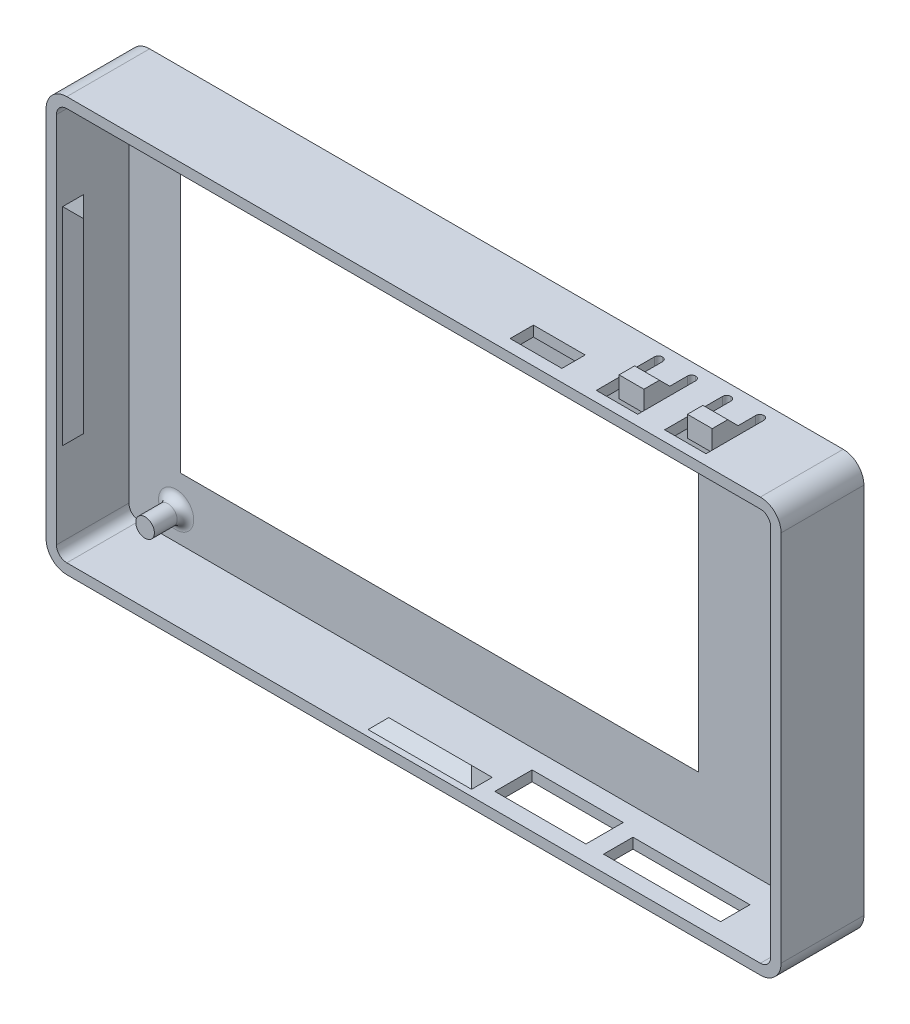
SolidWorks part; units mm, degrees
ref_plane "Front Plane" through (0, 0, 0) normal (0, 0, 1) x (1, 0, 0)
ref_plane "Top Plane" through (0, 0, 0) normal (0, 1, 0) x (1, 0, 0)
ref_plane "Right Plane" through (0, 0, 0) normal (1, 0, 0) x (0, 0, -1)
other "Graphic1"
other "Graphic (Closed) -1"
sketch "Sketch1" plane through (0, 0, 0) normal (0, 0, 1) x (1, 0, 0)
  line L1 (-33.5, 20) -> (33.5, 20)
  line L2 (-35.5, 18) -> (-35.5, -18)
  line L3 (-33.5, -20) -> (33.5, -20)
  line L4 (35.5, 18) -> (35.5, -18)
  line L5 (-35.5, 20) -> (35.5, -20) construction
  line L6 (-35.5, -20) -> (35.5, 20) construction
  arc A0 (35.5, 18) -> (33.5, 20) centre (33.5, 18) ccw
  arc A1 (35.5, -18) -> (33.5, -20) centre (33.5, -18) cw
  arc A2 (-33.5, -20) -> (-35.5, -18) centre (-33.5, -18) cw
  arc A3 (-35.5, 18) -> (-33.5, 20) centre (-33.5, 18) cw
  point P0 (0, 0)
  dimension "D3" = 2
  dimension "D1" = 71
  dimension "D2" = 40
extrude "Boss-Extrude1" add sketch "Sketch1" along normal blind 8
shell "Shell1" thickness 1
sketch "Sketch2" plane through (0, 0, 1) normal (0, 0, 1) x (1, 0, 0)
  line L0 (-35.5, 18) -> (-35.5, -18) construction
  line L1 (-29.5, 13) -> (20.5, 13)
  line L2 (-29.5, 13) -> (-29.5, -13)
  line L3 (-29.5, -13) -> (20.5, -13)
  line L4 (20.5, 13) -> (20.5, -13)
  line L5 (-29.5, 13) -> (20.5, -13) construction
  line L6 (-29.5, -13) -> (20.5, 13) construction
  point P0 (-4.5, 0)
  point P7 (-35.5, 0)
  dimension "D1" = 31
  dimension "D2" = 50
  dimension "D3" = 26
extrude "Cut-Extrude1" cut sketch "Sketch2" against normal through all
sketch "Sketch3" plane through (0, 19, 0) normal (0, -1, 0) x (1, 0, 0)
  line L0 (-33.5, 0) -> (33.5, 0) construction
  line L1 (8.15, 6.825) -> (13.15, 6.825)
  line L2 (8.15, 6.825) -> (8.15, 4.575)
  line L3 (8.15, 4.575) -> (13.15, 4.575)
  line L4 (13.15, 6.825) -> (13.15, 4.575)
  line L5 (8.15, 6.825) -> (13.15, 4.575) construction
  line L6 (8.15, 4.575) -> (13.15, 6.825) construction
  line L7 (33.5, 8) -> (33.5, 0) construction
  point P0 (10.65, 5.7)
  dimension "D1" = 5.7
  dimension "D2" = 22.85
  dimension "D3" = 5
  dimension "D4" = 2.25
extrude "Cut-Extrude2" cut sketch "Sketch3" against normal through all
sketch "Sketch4" plane through (0, 20, 0) normal (0, 1, 0) x (1, 0, 0)
  line L0 (33.5, -1) -> (-33.5, -1) construction
  line L1 (16.65, -1) -> (17.45, -1)
  line L2 (16.65, -1) -> (16.65, -7)
  line L3 (16.65, -7) -> (20.65, -7)
  line L4 (20.65, -1) -> (20.65, -7)
  line L5 (19.85, -1) -> (20.65, -1)
  line L7 (17.45, -1) -> (17.45, -5.6)
  line L8 (17.45, -5.6) -> (19.85, -5.6)
  line L9 (19.85, -1) -> (19.85, -5.6)
  line L10 (35.5, -8) -> (35.5, 0) construction
  line L11 (23.25, -1) -> (24.05, -1)
  line L12 (24.05, -1) -> (24.05, -5.6)
  line L13 (24.05, -5.6) -> (26.45, -5.6)
  line L14 (26.45, -1) -> (26.45, -5.6)
  line L15 (26.45, -1) -> (27.25, -1)
  line L16 (27.25, -1) -> (27.25, -7)
  line L17 (23.25, -7) -> (27.25, -7)
  line L18 (23.25, -1) -> (23.25, -7)
  dimension "D1" = 6
  dimension "D2" = 0.8
  dimension "D3" = 0.8
  dimension "D4" = 4
  dimension "D5" = 14.85
  dimension "D6" = 1.4
  dimension "D7" = 2
extrude "Cut-Extrude3" cut sketch "Sketch4" against normal up to surface (1 mm away) up to face at (10.65, 19, 5.7)
sketch "Sketch5" plane through (0, -20, 0) normal (0, -1, 0) x (1, 0, 0)
  line L0 (-33.5, 8) -> (33.5, 8) construction
  line L1 (6.3, 6.45) -> (15.1, 6.45)
  line L2 (6.3, 6.45) -> (6.3, 2.85)
  line L3 (6.3, 2.85) -> (15.1, 2.85)
  line L4 (15.1, 6.45) -> (15.1, 2.85)
  line L5 (35.5, 8) -> (35.5, 0) construction
  dimension "D1" = 8.8
  dimension "D2" = 3.6
  dimension "D3" = 1.55
  dimension "D4" = 20.4
extrude "Cut-Extrude4" cut sketch "Sketch5" against normal up to surface (1 mm away) up to face at (0, -19, 4.5)
fillet "Fillet1" radius 0.4 8 edges at (27.25, 19.5, 1) (26.45, 19.5, 1) (24.05, 19.5, 1) (23.25, 19.5, 1) (20.65, 19.5, 1) (19.85, 19.5, 1) (17.45, 19.5, 1) (16.65, 19.5, 1)
sketch "Sketch6" plane through (0, 20, 0) normal (0, 1, 0) x (1, 0, 0)
  line L0 (24.05, -5.6) -> (24.05, -1.4) construction
  line L1 (26.45, -5.6) -> (24.05, -5.6)
  line L2 (26.45, -5.6) -> (26.45, -4.1)
  line L3 (26.45, -4.1) -> (24.05, -4.1)
  line L4 (24.05, -5.6) -> (24.05, -4.1)
  line L5 (17.45, -5.6) -> (17.45, -1.4) construction
  line L6 (19.85, -5.6) -> (17.45, -5.6)
  line L7 (19.85, -5.6) -> (19.85, -4.1)
  line L8 (19.85, -4.1) -> (17.45, -4.1)
  line L9 (17.45, -5.6) -> (17.45, -4.1)
  dimension "D1" = 1.5
extrude "Boss-Extrude2" add sketch "Sketch6" along normal blind 1
chamfer "Chamfer1" distance 1 angle 45 2 edges at (18.65, 20, 4.1) (25.25, 20, 4.1)
sketch "Sketch7" plane through (0, -20, 0) normal (0, -1, 0) x (1, 0, 0)
  line L0 (15.1, 2.85) -> (15.1, 6.45) construction
  line L1 (16.8, 6.45) -> (28.1, 6.45)
  line L2 (16.8, 6.45) -> (16.8, 3.61)
  line L3 (16.8, 3.61) -> (28.1, 3.61)
  line L4 (28.1, 6.45) -> (28.1, 3.61)
  line L5 (15.1, 6.45) -> (6.3, 6.45) construction
  dimension "D1" = 1.7
  dimension "D2" = 11.3
  dimension "D3" = 2.84
extrude "Cut-Extrude5" cut sketch "Sketch7" against normal up to next
sketch "Sketch8" plane through (0, 0, 1) normal (0, 0, 1) x (1, 0, 0)
  line L0 (33.5, 20) -> (-33.5, 20) construction
  line L1 (-35.5, 18) -> (-35.5, -18) construction
  circle A0 centre (-29.94, 16.13) radius 0.9
  dimension "D3" = 1.8
  dimension "D1" = 3.87
  dimension "D2" = 5.56
extrude "Boss-Extrude3" add sketch "Sketch8" along normal blind 3
pattern_linear "LPattern1" count 2 spacing 61.45 along (1, 0, 0) count 2 spacing 32.4 along (0, -1, 0) of "Boss-Extrude3"
sketch "Sketch9" plane through (0, -19, 0) normal (0, 1, 0) x (1, 0, 0)
  line L0 (-33.5, -8) -> (33.5, -8) construction
  line L1 (5, -7.4) -> (-5, -7.4)
  line L2 (5, -7.4) -> (5, -5.4)
  line L3 (5, -5.4) -> (-5, -5.4)
  line L4 (-5, -7.4) -> (-5, -5.4)
  line L5 (6.3, -6.45) -> (6.3, -2.85) construction
  dimension "D1" = 2
  dimension "D2" = 10
  dimension "D3" = 0.6
  dimension "D4" = 1.3
extrude "Boss-Extrude4" add sketch "Sketch9" along normal blind 2 draft 45
mirror "Mirror1" about plane through (0, 0, 0) normal (0, 1, 0) of "Boss-Extrude4"
sketch "Sketch10" plane through (-34.5, 0, 0) normal (1, 0, 0) x (0, 0, -1)
  line L0 (0, -18) -> (0, 18) construction
  line L1 (-7.4, 10) -> (-5.4, 10)
  line L2 (-7.4, 10) -> (-7.4, -10)
  line L3 (-7.4, -10) -> (-5.4, -10)
  line L4 (-5.4, 10) -> (-5.4, -10)
  line L5 (-8, 20) -> (0, 20) construction
  dimension "D1" = 5.4
  dimension "D2" = 2
  dimension "D3" = 20
  dimension "D4" = 10
extrude "Boss-Extrude5" add sketch "Sketch10" along normal blind 2 draft 45
mirror "Mirror2" about plane through (0, 0, 0) normal (1, 0, 0) of "Boss-Extrude5"
chamfer "Chamfer2" distance 1 angle 45 4 edges at (20.5, 0, 0) (-4.5, 13, 0) (-29.5, 0, 0) (-4.5, -13, 0)
fillet "Fillet2" radius 0.8 4 edges at (-29.04, 16.13, 1) (32.41, 16.13, 1) (-29.04, -16.27, 1) (32.41, -16.27, 1)
equation "\"D3@Sketch4\"=\"D2@Sketch4\""
